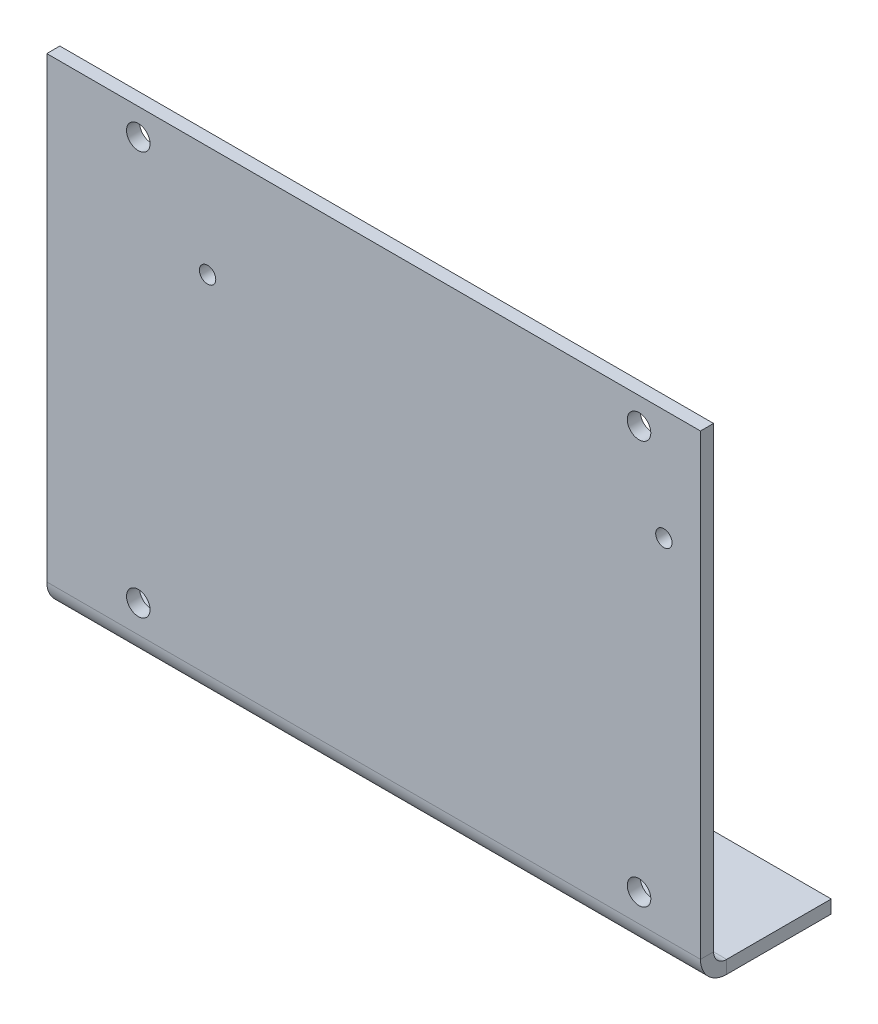
SolidWorks part; units mm, degrees
note: The reader was unsure of these and kept them because the rebuilt part matched: flange length of "Edge-Flange1".
ref_plane "Front Plane" through (0, 0, 0) normal (0, 0, 1) x (1, 0, 0)
ref_plane "Top Plane" through (0, 0, 0) normal (0, 1, 0) x (1, 0, 0)
ref_plane "Right Plane" through (0, 0, 0) normal (1, 0, 0) x (0, 0, -1)
sketch "Sketch1" plane through (0, 0, 0) normal (0, 1, 0) x (1, 0, 0)
  line L1 (-50, 10) -> (50, 10)
  line L2 (-50, 10) -> (-50, -10)
  line L3 (-50, -10) -> (50, -10)
  line L4 (50, 10) -> (50, -10)
  line L5 (-50, 10) -> (50, -10) construction
  line L6 (-50, -10) -> (50, 10) construction
  point P0 (0, 0)
  dimension "D1" = 100
  dimension "D2" = 20
base flange "Base-Flange1" sketch "Sketch1" thickness 2 reverse thickness direction no parameters "D1"=2
edge flange "Edge-Flange1" sketch "Sketch8" flange angle 90 flange length 74 flange position material inside bend radius 2 thickness 2 relief rectangular parameters "D6"=10
sketch "Sketch8" plane through (0, 0, 10) normal (0, 0, 1) x (1, 0, 0)
  line L0 (-50, 0) -> (50, 0) construction
  line L1 (-50, 0) -> (50, 0)
  line L2 (-50, 0) -> (-50, 72)
  line L3 (-50, 72) -> (50, 72)
  line L4 (50, 72) -> (50, 0)
bend "EdgeBend1" bend radius 2 bend angle 90 parameters "D5"=1
hole_wizard "M3.5 Clearance Hole1" positions "Sketch9" profile "Sketch10" hole size "M3" standard "AS"
sketch "Sketch9" plane through (114.4715, -206.958, 10) normal (0, 0, 1) x (1, 0, 0)
  point P0 (-139.8715, 261.958)
  point P3 (-70.0715, 261.958)
sketch "Sketch10" plane through (-25.4, 55, 10) normal (1, 0, 0) x (0, -1, 0)
  line L0 (0, 0) -> (0, 2.7501)
  line L1 (0, 2.7501) -> (1.25, 1.999)
  line L2 (1.25, 1.999) -> (1.25, 0)
  line L3 (1.25, 0) -> (0, 0)
  line L4 (0, 2.7501) -> (-1.25, 1.999) construction
  line L5 (0, -6.35) -> (0, 107.95) construction
  dimension "Hole Dia." = 2.5
  dimension "Hole Depth" = 1.999
  dimension "Drill Angle" = 118
hole_wizard "M3 Clearance Hole1" positions "Sketch12" profile "Sketch13" hole size "M3" standard "AS" end condition through all
sketch "Sketch12" plane through (114.4715, -206.958, 8) normal (0, 0, 1) x (1, 0, 0)
  point P0 (-150.4715, 274.893)
  point P3 (-73.8715, 274.893)
  point P6 (-73.8715, 213.173)
  point P9 (-150.4715, 213.173)
sketch "Sketch13" plane through (-36, 67.935, 8) normal (1, 0, 0) x (0, 1, 0)
  line L0 (0, 0) -> (0, 2)
  line L1 (0, 2) -> (1.8, 2)
  line L2 (1.8, 2) -> (1.8, 0)
  line L3 (1.8, 0) -> (0, 0)
  line L4 (0, -6.35) -> (0, 107.95) construction
  dimension "Thru Hole Dia." = 3.6
  dimension "Thru Hole Depth" = 2
sketch "Bend-Lines1" [suppressed] plane through (0, 0, 0) normal (0, 1, 0) x (1, 0, 0)
sketch "Bounding-Box1" [suppressed] plane through (0, 0, 0) normal (0, 1, 0) x (1, 0, 0)
sheet metal parameters "Sheet-Metal1" thickness 2 parameters "D1"=2
flat pattern "Flat-Pattern1" [suppressed]
sketch "Bend-Lines2" plane through (0, 0, 0) normal (0, 1, 0) x (1, 0, 0)
sketch3d "Bounding-Box2" [suppressed]
  line L0 (-40, -10, 0) -> (40, -10, 0) construction
  line L1 (-40, 10, 0) -> (40, 10, 0) construction
  line L2 (-40, -10, 0) -> (-40, 10, 0) construction
  line L3 (40, -10, 0) -> (40, 10, 0) construction
sheet metal parameters "Sheet-Metal2" thickness 2 parameters "D1"=2
flat pattern "Flat-Pattern1"
sketch "Bend-Lines2" plane through (0, 0, 0) normal (0, 1, 0) x (1, 0, 0)
  line L0 (-50, -8.3562) -> (50, -8.3562) construction
  line L1 (-50, -8.3562) -> (50, -8.3562) construction
sketch3d "Bounding-Box2" [suppressed]
  line L0 (50, -80.7124, 0) -> (-50, -80.7124, 0) construction
  line L1 (50, 10, 0) -> (-50, 10, 0) construction
  line L2 (50, -80.7124, 0) -> (50, 10, 0) construction
  line L3 (-50, -80.7124, 0) -> (-50, 10, 0) construction
bend of the flat pattern "Flatten-<EdgeBend1>1"
sheet metal parameters "Sheet-Metal3" thickness 2 parameters "D1"=2
flat pattern "Flat-Pattern1"
sketch "Bend-Lines2" plane through (0, 0, 0) normal (0, 1, 0) x (1, 0, 0)
  line L0 (-50, -8.3562) -> (50, -8.3562) construction
  line L1 (-50, -8.3562) -> (50, -8.3562) construction
sketch3d "Bounding-Box2" [suppressed]
  line L0 (50, -81.7124, 0) -> (-50, -81.7124, 0) construction
  line L1 (50, 10, 0) -> (-50, 10, 0) construction
  line L2 (50, -81.7124, 0) -> (50, 10, 0) construction
  line L3 (-50, -81.7124, 0) -> (-50, 10, 0) construction
bend of the flat pattern "Flatten-<EdgeBend1>1"
sheet metal parameters "Sheet-Metal5" thickness 2 parameters "D1"=2
flat pattern "Flat-Pattern1"
sketch "Bend-Lines2" plane through (0, 0, 0) normal (0, 1, 0) x (1, 0, 0)
  line L0 (-50, -8.3562) -> (50, -8.3562) construction
  line L1 (-50, -8.3562) -> (50, -8.3562) construction
sketch3d "Bounding-Box2" [suppressed]
  line L0 (50, -80.7124, 0) -> (-50, -80.7124, 0) construction
  line L1 (50, 10, 0) -> (-50, 10, 0) construction
  line L2 (50, -80.7124, 0) -> (50, 10, 0) construction
  line L3 (-50, -80.7124, 0) -> (-50, 10, 0) construction
bend of the flat pattern "Flatten-<EdgeBend1>1"
